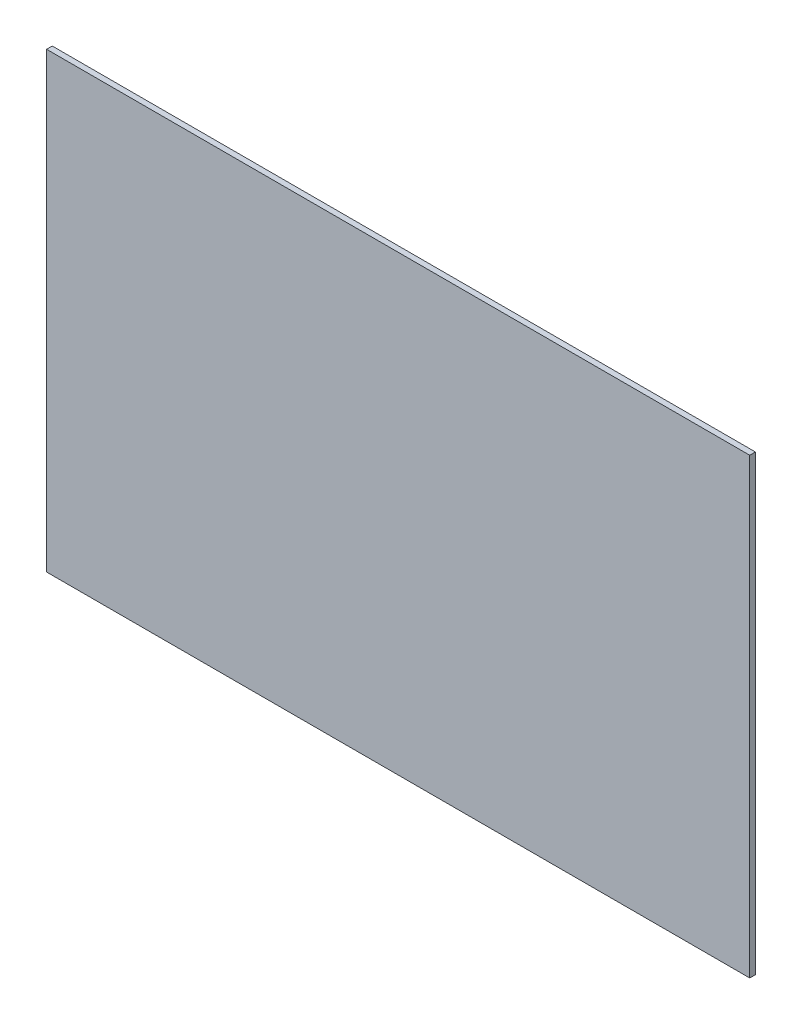
SolidWorks part; units mm, degrees
ref_plane "Front Plane" through (0, 0, 0) normal (0, 0, 1) x (1, 0, 0)
ref_plane "Top Plane" through (0, 0, 0) normal (0, 1, 0) x (1, 0, 0)
ref_plane "Right Plane" through (0, 0, 0) normal (1, 0, 0) x (0, 0, -1)
sketch "Sketch1" plane through (0, 0, 0) normal (0, 0, 1) x (1, 0, 0)
  line L1 (-196.85, -126.746) -> (196.85, -126.746)
  line L2 (-196.85, -126.746) -> (-196.85, 126.746)
  line L3 (-196.85, 126.746) -> (196.85, 126.746)
  line L4 (196.85, -126.746) -> (196.85, 126.746)
  line L5 (0, 126.746) -> (0, -126.746) construction
  line L6 (-196.85, 0) -> (196.85, 0) construction
  point P0 (0, 0)
  point P4 (-137.795, 0)
  point P5 (137.795, 0)
  point P6 (0, 88.7222)
  point P7 (0, -88.7222)
  dimension "Length" = 393.7
  dimension "Width" = 253.492
  dimension "Break" = 59.055
  dimension "D2" = 59.055
  dimension "D1" = 38.0238
  dimension "D3" = 38.0238
sketch "Sketch2" plane through (0, 0, 0) normal (1, 0, 0) x (0, 0, -1)
  line L0 (-1.5875, -126.746) -> (1.5875, -126.746)
  dimension "Thickness" = 3.175
sketch "Sketch3" plane through (0, 0, 0) normal (0, 0, 1) x (1, 0, 0)
  line L0 (-196.85, -126.746) -> (-196.85, 126.746) construction
  line L1 (-196.85, -126.746) -> (196.85, -126.746) construction
  line L2 (196.85, -126.746) -> (196.85, 126.746) construction
  line L3 (-196.85, 126.746) -> (196.85, 126.746) construction
  line L4 (-196.85, -126.746) -> (-196.85, 126.746)
  line L5 (-196.85, -126.746) -> (196.85, -126.746)
  line L6 (196.85, -126.746) -> (196.85, 126.746)
  line L7 (-196.85, 126.746) -> (196.85, 126.746)
extrude "Boss-Extrude1" add sketch "Sketch3" along normal mid plane 3.175
equation "\"D1@Boss-Extrude1\"=\"thickness@sketch2\""
equation "\"Break@Sketch1\" = \"Length@Sketch1\" * 0.15"
equation "\"D2@Sketch1\" = \"Break@Sketch1\""
equation "\"D1@Sketch1\"=\"Width@Sketch1\"*0.15"
equation "\"D3@Sketch1\"=\"D1@Sketch1\""
